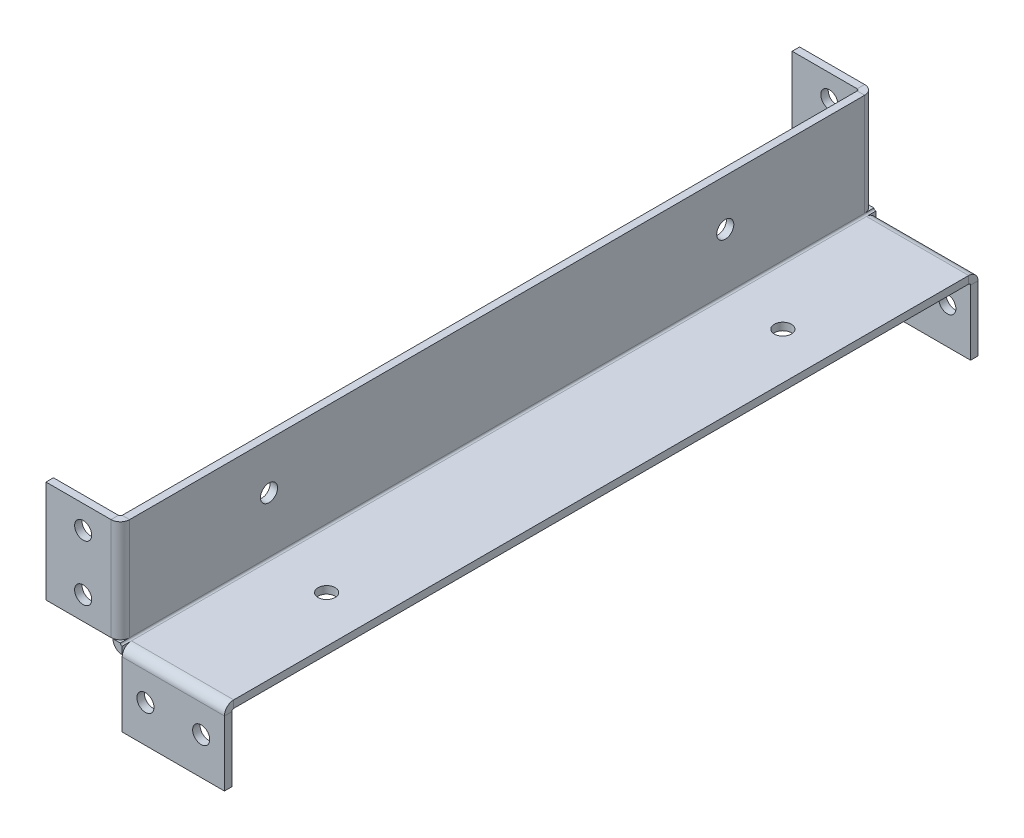
SolidWorks part; units mm, degrees
note: The reader was unsure of these and kept them because the rebuilt part matched: flange length of "Edge-Flange1", "Edge-Flange2".
ref_plane "Front Plane" through (0, 0, 0) normal (0, 0, 1) x (1, 0, 0)
ref_plane "Top Plane" through (0, 0, 0) normal (0, 1, 0) x (1, 0, 0)
ref_plane "Right Plane" through (0, 0, 0) normal (1, 0, 0) x (0, 0, -1)
sketch "Sketch1" plane through (0, 0, 0) normal (0, 1, 0) x (1, 0, 0)
  line L1 (30, 202.75) -> (-30, 202.75)
  line L2 (30, 202.75) -> (30, -202.75)
  line L3 (30, -202.75) -> (-30, -202.75)
  line L4 (-30, 202.75) -> (-30, -202.75)
  line L5 (30, 202.75) -> (-30, -202.75) construction
  line L6 (30, -202.75) -> (-30, 202.75) construction
  point P0 (0, 0)
  dimension "D1" = 60
  dimension "D2" = 405.5
sheet metal parameters "Sheet-Metal1" thickness 4 parameters "D1"=1
base flange "Base-Flange1" sketch "Sketch1" thickness 4 reverse thickness direction yes parameters "D1"=1
edge flange "Edge-Flange1" sketch "Sketch5" flange angle 90 flange length 60 flange position material inside bend radius 1 thickness 4 parameters "D6"=10
sketch "Sketch5" plane through (-30, 4, 0) normal (-1, 0, 0) x (0, 0, 1)
  line L2 (-202.75, 0) -> (-202.75, 56)
  line L3 (-202.75, 56) -> (202.75, 56)
  line L4 (202.75, 56) -> (202.75, 0)
  line L5 (-202.75, 0) -> (202.75, 0) construction
  line L6 (-202.75, 0) -> (202.75, 0)
bend "EdgeBend1" bend radius 1 bend angle 90 parameters "D5"=1
edge flange "Edge-Flange2" sketch "Sketch14" flange profiles "Sketch14", "Sketch15", "Sketch16", "Sketch17" flange angle 90 flange length 40 flange position material inside bend radius 1 thickness 4 relief none parameters "D6"=10, "D8"=0.5
sketch "Sketch14" plane through (-30, 0, 202.75) normal (0, 0, -1) x (0, -1, 0)
  line L1 (-5, 0) -> (-60, 0) construction
  line L2 (-60, 0) -> (-60, 36)
  line L3 (-60, 36) -> (-5, 36)
  line L4 (-5, 36) -> (-5, 0)
  line L5 (-5, 0) -> (-60, 0)
sketch "Sketch15" plane through (0, 0, 202.75) normal (0, 0, -1) x (1, 0, 0)
  line L0 (30, 0) -> (-25, 0) construction
  line L1 (30, 0) -> (-25, 0)
  line L2 (30, 0) -> (30, 36)
  line L3 (30, 36) -> (-25, 36)
  line L4 (-25, 36) -> (-25, 0)
sketch "Sketch16" plane through (-30, 0, -202.75) normal (0, 0, 1) x (0, 1, 0)
  line L0 (60, 0) -> (5, 0) construction
  line L1 (60, 0) -> (5, 0)
  line L2 (60, 0) -> (60, 36)
  line L3 (60, 36) -> (5, 36)
  line L4 (5, 36) -> (5, 0)
sketch "Sketch17" plane through (0, 0, -202.75) normal (0, 0, 1) x (-1, 0, 0)
  line L0 (25, 0) -> (-30, 0) construction
  line L1 (25, 0) -> (-30, 0)
  line L2 (25, 0) -> (25, 36)
  line L3 (25, 36) -> (-30, 36)
  line L4 (-30, 36) -> (-30, 0)
bend "EdgeBend2" bend radius 1 bend angle 90 parameters "D5"=2
bend "EdgeBend3" bend radius 1 bend angle 90 parameters "D5"=3
bend "EdgeBend4" bend radius 1 bend angle 90 parameters "D5"=4
bend "EdgeBend5" bend radius 1 bend angle 90 parameters "D5"=5
sketch "Sketch18" plane through (0, 0, 202.75) normal (0, 0, 1) x (1, 0, 0)
  line L0 (-25, 4) -> (30, 4) construction
  line L1 (-26, 60) -> (-26, 5) construction
  line L2 (-66, 60) -> (-31, 60) construction
  line L3 (30, -1) -> (30, -36) construction
  circle A0 centre (-46, 47.5) radius 4.6
  circle A1 centre (-46, 17.5) radius 4.6
  circle A2 centre (-12.5, -16) radius 4.6
  circle A3 centre (17.5, -16) radius 4.6
  dimension "D7" = 9.2
  dimension "D1" = 30
  dimension "D2" = 30
  dimension "D3" = 20
  dimension "D4" = 20
  dimension "D5" = 12.5
  dimension "D6" = 12.5
extrude "Extrude1" cut sketch "Sketch18" against normal through all normal cut yes
sketch "Sketch19" plane through (-26, 0, 0) normal (1, 0, 0) x (0, 0, -1)
  line L0 (-197.75, 60) -> (197.75, 60) construction
  line L1 (-202.75, 5) -> (-202.75, 60) construction
  line L2 (202.75, 5) -> (202.75, 60) construction
  circle A0 centre (-122.75, 35) radius 4.6
  circle A1 centre (122.75, 35) radius 4.6
  dimension "D4" = 9.2
  dimension "D1" = 25
  dimension "D2" = 80
  dimension "D3" = 80
extrude "Extrude2" cut sketch "Sketch19" against normal blind 4 normal cut yes
sketch "Sketch20" plane through (0, 4, 0) normal (0, 1, 0) x (1, 0, 0)
  line L0 (30, -197.75) -> (30, 197.75) construction
  line L1 (-25, -202.75) -> (30, -202.75) construction
  line L2 (30, 202.75) -> (-25, 202.75) construction
  circle A0 centre (5, 122.75) radius 4.6
  circle A1 centre (5, -122.75) radius 4.6
  dimension "D2" = 9.2
  dimension "D1" = 25
  dimension "D3" = 80
  dimension "D4" = 80
extrude "Extrude3" cut sketch "Sketch20" against normal blind 4 normal cut yes
flat pattern "Flat-Pattern1" [suppressed]
sketch "Bend-Lines1" plane through (0, 4, 0) normal (0, 1, 0) x (-1, 0, 0)
  line L0 (25, -199.4012) -> (-30, -199.4012) construction
  line L1 (82.8023, -199.4012) -> (27.8023, -199.4012) construction
  line L2 (-30, 199.4012) -> (25, 199.4012) construction
  line L3 (27.8023, 199.4012) -> (82.8023, 199.4012) construction
  line L4 (26.4012, -203) -> (26.4012, 203) construction
  line L5 (25, -199.4012) -> (-30, -199.4012) construction
  line L6 (82.8023, -199.4012) -> (27.8023, -199.4012) construction
  line L7 (-30, 199.4012) -> (25, 199.4012) construction
  line L8 (27.8023, 199.4012) -> (82.8023, 199.4012) construction
  line L9 (26.4012, -203) -> (26.4012, 203) construction
sketch3d "Bounding-Box1" [suppressed]
  line L0 (52.8023, 32.8023, 0) -> (52.8023, -438.8023, 0) construction
  line L1 (-60, 32.8023, 0) -> (-60, -438.8023, 0) construction
  line L2 (52.8023, 32.8023, 0) -> (-60, 32.8023, 0) construction
  line L3 (52.8023, -438.8023, 0) -> (-60, -438.8023, 0) construction
bend of the flat pattern "Flatten-<EdgeBend1>1"
bend of the flat pattern "Flatten-<EdgeBend2>1"
bend of the flat pattern "Flatten-<EdgeBend3>1"
bend of the flat pattern "Flatten-<EdgeBend4>1"
bend of the flat pattern "Flatten-<EdgeBend5>1"
